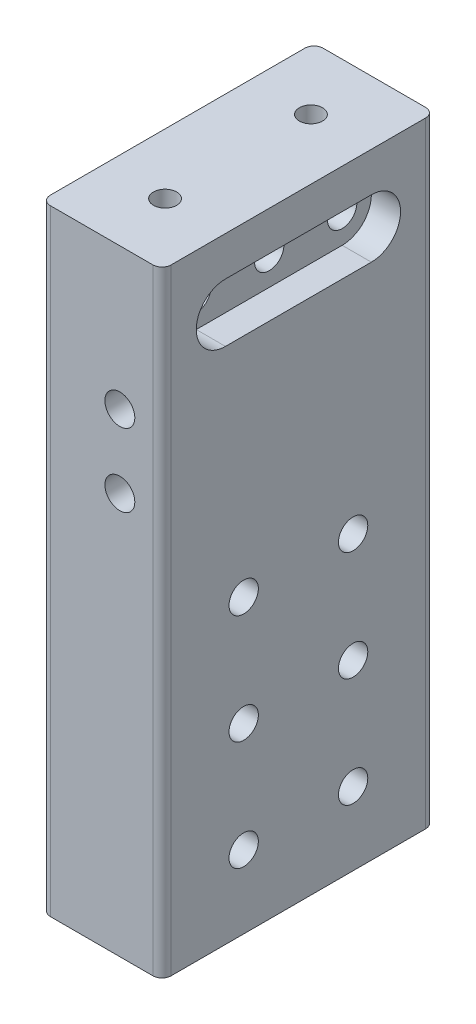
SolidWorks part; units mm, degrees
material "6061-T6 (SS)"
ref_plane "Front Plane" through (0, 0, 0) normal (0, 0, 1) x (1, 0, 0)
ref_plane "Top Plane" through (0, 0, 0) normal (0, 1, 0) x (1, 0, 0)
ref_plane "Right Plane" through (0, 0, 0) normal (1, 0, 0) x (0, 0, -1)
sketch "Sketch1" plane through (0, 0, 0) normal (0, 1, 0) x (1, 0, 0)
  line L1 (-10.5156, -23.7427) -> (10.5156, -23.7427)
  line L2 (-10.5156, -23.7427) -> (-10.5156, 23.7426)
  line L3 (-10.5156, 23.7426) -> (10.5156, 23.7426)
  line L4 (10.5156, -23.7427) -> (10.5156, 23.7426)
  line L5 (-10.5156, -23.7427) -> (10.5156, 23.7426) construction
  line L6 (-10.5156, 23.7426) -> (10.5156, -23.7427) construction
  point P0 (0, 0)
  dimension "D1" = 21.0312
  dimension "D2" = 47.4853
extrude "Boss-Extrude1" add sketch "Sketch1" along normal mid plane 101.6
sketch "Sketch2" plane through (0, 0, 23.7427) normal (0, 0, 1) x (1, 0, 0)
  line L5 (-10.5156, 50.8) -> (10.5156, 50.8) construction
  circle A1 centre (3.175, 19.05) radius 2.6035
  circle A2 centre (3.175, 31.75) radius 2.6035
  dimension "D3" = 19.05
  dimension "D1" = 7.3406
  dimension "D2" = 5.207
  dimension "D4" = 12.7
extrude "Cut-Extrude1" cut sketch "Sketch2" against normal through all
sketch "Sketch4" plane through (10.5156, 0, 0) normal (1, 0, 0) x (0, 0, -1)
  line L0 (-23.7427, 50.8) -> (23.7426, 50.8) construction
  circle A0 centre (-12.7, 44.45) radius 2.5527
  circle A1 centre (12.7, 44.45) radius 2.5527
  circle A2 centre (0, 44.45) radius 2.5527
  dimension "D5" = 5.1054
  dimension "D1" = 6.35
  dimension "D3" = 12.7
  dimension "D4" = 12.7
extrude "Cut-Extrude3" cut sketch "Sketch4" against normal through all
fillet "Fillet1" radius 1.5875 4 edges at (10.5156, 0, 23.7427) (-10.5156, 0, 23.7427) (-10.5156, 0, -23.7426) (10.5156, 0, -23.7426)
sketch "Sketch7" plane through (10.5156, 0, 0) normal (1, 0, 0) x (0, 0, -1)
  line L0 (-12.7, 44.45) -> (12.7, 44.45) construction
  line L1 (-12.7, 49.53) -> (12.7, 49.53)
  line L2 (-12.7, 39.37) -> (12.7, 39.37)
  arc A0 (-12.7, 49.53) -> (-12.7, 39.37) centre (-12.7, 44.45) ccw
  arc A1 (12.7, 39.37) -> (12.7, 49.53) centre (12.7, 44.45) ccw
  point P4 (0, 44.45)
  dimension "D1" = 5.08
extrude "Cut-Extrude5" cut sketch "Sketch7" against normal blind 5.08
sketch "Sketch8" plane through (0, 50.8, 0) normal (0, 1, 0) x (1, 0, 0)
  line L4 (-8.9281, -23.7427) -> (8.9281, -23.7427)
  line L5 (10.5156, -22.1552) -> (10.5156, 22.1551)
  line L6 (8.9281, 23.7426) -> (-8.9281, 23.7426)
  line L7 (-10.5156, 22.1551) -> (-10.5156, -22.1552)
  line L8 (-8.9281, -23.7427) -> (8.9281, -23.7427)
  line L9 (10.5156, -22.1552) -> (10.5156, 22.1551)
  line L10 (8.9281, 23.7426) -> (-8.9281, 23.7426)
  line L11 (-10.5156, 22.1551) -> (-10.5156, -22.1552)
  arc A4 (8.9281, -23.7427) -> (10.5156, -22.1552) centre (8.9281, -22.1552) ccw
  arc A5 (10.5156, 22.1551) -> (8.9281, 23.7426) centre (8.9281, 22.1551) ccw
  arc A6 (-8.9281, 23.7426) -> (-10.5156, 22.1551) centre (-8.9281, 22.1551) ccw
  arc A7 (-8.9281, 23.7426) -> (-10.5156, 22.1551) centre (-8.9281, 22.1551) ccw
  arc A8 (8.9281, -23.7427) -> (10.5156, -22.1552) centre (8.9281, -22.1552) ccw
  arc A9 (10.5156, 22.1551) -> (8.9281, 23.7426) centre (8.9281, 22.1551) ccw
  arc A10 (-10.5156, -22.1552) -> (-8.9281, -23.7427) centre (-8.9281, -22.1552) ccw
  arc A11 (-10.5156, -22.1552) -> (-8.9281, -23.7427) centre (-8.9281, -22.1552) ccw
  dimension "D1" = 0
extrude "Boss-Extrude2" add sketch "Sketch8" along normal blind 5.588
sketch "Sketch9" plane through (0, 56.388, 0) normal (0, 1, 0) x (1, 0, 0)
  line L0 (-10.5156, 0) -> (10.5156, 0) construction
  line L1 (-10.5156, 22.1551) -> (-10.5156, -22.1552) construction
  line L2 (10.5156, -22.1552) -> (10.5156, 22.1551) construction
  circle A0 centre (0, 12.7) radius 2.0193
  circle A2 centre (0, -12.7) radius 2.0193
  dimension "D2" = 4.0386
  dimension "D1" = 12.7
  dimension "D3" = 10.5156
extrude "Cut-Extrude6" cut sketch "Sketch9" against normal blind 5.08
sketch "Sketch10" plane through (10.5156, 0, 0) normal (1, 0, 0) x (0, 0, -1)
  line L0 (0, 0) -> (0, -50.8) construction
  line L1 (-22.1552, -50.8) -> (22.1551, -50.8) construction
  circle A0 centre (-9.525, -38.1) radius 2.5527
  circle A1 centre (-9.525, -19.05) radius 2.5527
  circle A2 centre (-9.525, 0) radius 2.5527
  circle A3 centre (9.525, 0) radius 2.5527
  circle A4 centre (9.525, -19.05) radius 2.5527
  circle A5 centre (9.525, -38.1) radius 2.5527
  dimension "D1" = 5.1054
  dimension "D6" = 12.7
  dimension "D2" = 19.05
  dimension "D3" = 19.05
  dimension "D4" = 9.525
  dimension "D5" = 9.525
extrude "Cut-Extrude7" cut sketch "Sketch10" against normal through all
